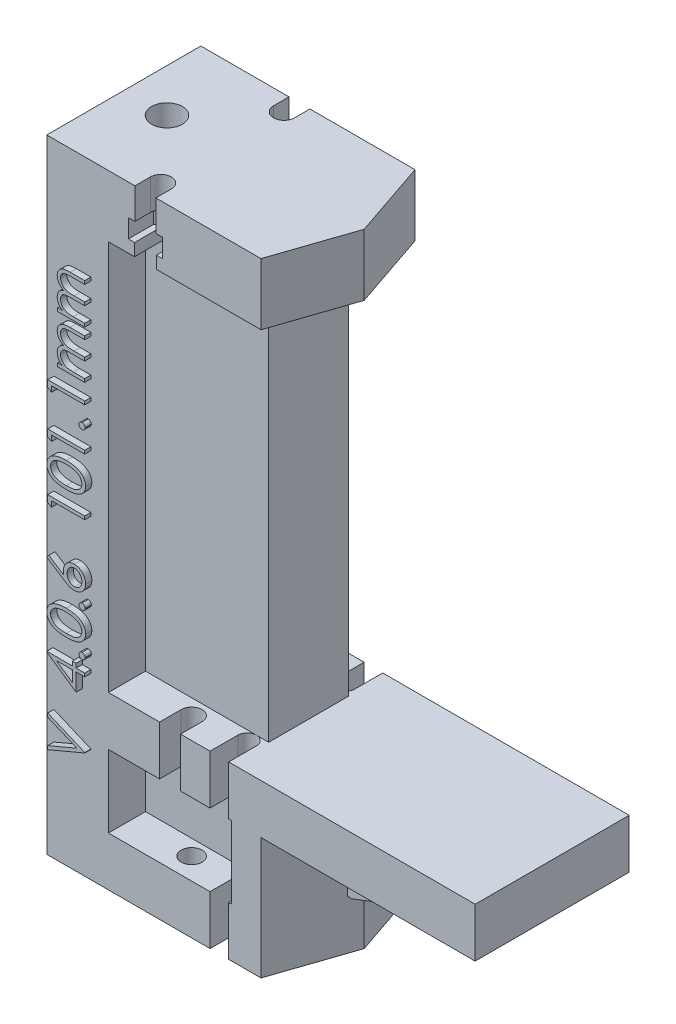
SolidWorks part; units mm, degrees
material "ABS"
ref_plane "Front" through (0, 0, 0) normal (0, 0, 1) x (1, 0, 0)
ref_plane "Top" through (0, 0, 0) normal (0, 1, 0) x (1, 0, 0)
ref_plane "Right" through (0, 0, 0) normal (1, 0, 0) x (0, 0, -1)
sketch "Sketch6" plane through (0, 0, 0) normal (0, 0, 1) x (1, 0, 0)
  line L0 (-25, 50.55) -> (15, 50.55)
  line L1 (15, 50.55) -> (15, 42.55)
  line L2 (15, 42.55) -> (-15, 42.55)
  line L3 (-15, 42.55) -> (-15, -42.55)
  line L4 (-15, -42.55) -> (25, -42.55)
  line L5 (25, -42.55) -> (25, -50.55)
  line L6 (25, -50.55) -> (-25, -50.55)
  line L7 (-25, -50.55) -> (-25, 50.55)
  line L8 (-25, 50.55) -> (25, -50.55) construction
  dimension "D1" = 101.1
  dimension "D2" = 8
  dimension "D3" = 10
  dimension "D4" = 50
  dimension "D5" = 40
extrude "Boss-Extrude2" add sketch "Sketch6" along normal mid plane 25
sketch "Sketch15" plane through (0, 0, 12.5) normal (0, 0, 1) x (1, 0, 0)
  line L0 (-15, -22.805) -> (15, -22.805)
  line L1 (-15, -42.55) -> (-15, 42.55) construction
  line L2 (-15, -30.805) -> (5, -30.805)
  line L3 (5, -50.55) -> (15, -50.55)
  line L4 (15, -50.55) -> (15, -22.805)
  line L5 (-25, -50.55) -> (25, -50.55) construction
  line L6 (-15, -30.805) -> (-15, -22.805)
  line L7 (5, -50.55) -> (5, -30.805)
  dimension "D2" = 8
extrude "Boss-Extrude3" add sketch "Sketch15" against normal up to surface (25 mm away) up to face at (0, 0, -12.5)
sketch "Sketch20" plane through (0, 50.55, 0) normal (0, 1, 0) x (1, 0, 0)
  line L0 (-10.7, 12.5) -> (-10.7, 10)
  line L1 (15, 12.5) -> (-25, 12.5) construction
  line L2 (-7.3, 10) -> (-7.3, 12.5)
  line L3 (-7.3, 12.5) -> (-10.7, 12.5)
  line L4 (0, 0) -> (15, 0) construction
  line L5 (15, -12.5) -> (15, 12.5) construction
  line L6 (-7.3, -12.5) -> (-10.7, -12.5)
  line L7 (-7.3, -10) -> (-7.3, -12.5)
  line L8 (-10.7, -12.5) -> (-10.7, -10)
  line L9 (-9, -10) -> (-9, 10) construction
  arc A0 (-10.7, 10) -> (-7.3, 10) centre (-9, 10) ccw
  arc A1 (-10.7, -10) -> (-7.3, -10) centre (-9, -10) cw
  dimension "D1" = 1.7
  dimension "D2" = 20
extrude "Cut-Extrude2" cut sketch "Sketch20" against normal up to next
sketch "Sketch21" plane through (0, -50.55, 0) normal (0, -1, 0) x (1, 0, 0)
  line L0 (-6.7, 12.5) -> (-6.7, 9)
  line L1 (-25, 12.5) -> (25, 12.5) construction
  line L2 (-3.3, 9) -> (-3.3, 12.5)
  line L3 (-3.3, 12.5) -> (-6.7, 12.5) construction
  line L4 (-5, -9) -> (-5, 9) construction
  line L5 (-6.7, 12.5) -> (-3.3, 12.5)
  line L7 (-3.3, -12.5) -> (-6.7, -12.5)
  line L8 (-3.3, -9) -> (-3.3, -12.5)
  line L9 (-6.7, -12.5) -> (-6.7, -9)
  arc A0 (-6.7, 9) -> (-3.3, 9) centre (-5, 9) ccw
  arc A1 (-6.7, -9) -> (-3.3, -9) centre (-5, -9) cw
  dimension "D1" = 1.7
  dimension "D2" = 18
extrude "Cut-Extrude3" cut sketch "Sketch21" against normal up to surface (27.745 mm away) up to face at (0, -22.805, 0)
sketch "Sketch22" plane through (0, 0, 0) normal (0, 0, 1) x (1, 0, 0)
  line L0 (-15, 21.805) -> (11, 42.55)
  line L1 (-7.3, 42.55) -> (15, 42.55) construction
  line L2 (-15, 42.55) -> (11, 42.55)
  line L5 (-15, -22.805) -> (-15, 42.55) construction
  line L7 (-15, 42.55) -> (-10.7, 42.55) construction
  line L8 (-15, 42.55) -> (-15, 21.805)
extrude "Boss-Extrude5" [suppressed] add sketch "Sketch22" along normal mid plane 4
sketch "Sketch23" plane through (0, 50.55, 0) normal (0, 1, 0) x (1, 0, 0)
  line L0 (-2.51, 12.5) -> (-2.51, 9)
  line L1 (15, 12.5) -> (-7.3, 12.5) construction
  line L2 (0.51, 9) -> (0.51, 12.5)
  line L3 (0.51, 12.5) -> (-2.51, 12.5)
  line L4 (-9, 10) -> (-1, 10) construction
  line L5 (-1, 10) -> (-1, 9) construction
  line L6 (0, 0) -> (12, 0) construction
  line L8 (0.51, -12.5) -> (-2.51, -12.5)
  line L9 (0.51, -9) -> (0.51, -12.5)
  line L10 (-2.51, -12.5) -> (-2.51, -9)
  line L11 (15, -12.5) -> (15, 12.5) construction
  arc A0 (-2.51, 9) -> (0.51, 9) centre (-1, 9) ccw
  arc A1 (-2.51, -9) -> (0.51, -9) centre (-1, -9) cw
  dimension "D1" = 1.51
  dimension "D2" = 8
  dimension "D3" = 1
  dimension "D4" = 3
extrude "Cut-Extrude4" [suppressed] cut sketch "Sketch23" against normal up to next
sketch "Sketch24" plane through (0, -50.55, 0) normal (0, -1, 0) x (1, 0, 0)
  line L0 (1.49, -12.5) -> (1.49, -8)
  line L1 (-3.3, -12.5) -> (25, -12.5) construction
  line L2 (4.51, -8) -> (4.51, -12.5)
  line L3 (4.51, -12.5) -> (1.49, -12.5)
  line L4 (3, -8) -> (3, -9) construction
  line L5 (3, -9) -> (-5, -9) construction
  line L9 (4.51, 12.5) -> (1.49, 12.5)
  line L10 (4.51, 8) -> (4.51, 12.5)
  line L11 (1.49, 12.5) -> (1.49, 8)
  arc A0 (1.49, -8) -> (4.51, -8) centre (3, -8) cw
  arc A1 (1.49, 8) -> (4.51, 8) centre (3, 8) ccw
  dimension "D2" = 8
  dimension "D3" = 1
extrude "Cut-Extrude6" cut sketch "Sketch24" against normal up to surface (27.745 mm away) up to face at (-3.3333, -22.805, 0)
sketch "Sketch28" plane through (0, 50.55, 0) normal (0, 1, 0) x (1, 0, 0)
  line L0 (-10.7, 10) -> (-7.3, 10) construction
  line L1 (-10.7, -10) -> (-7.3, -10) construction
  line L2 (-7.3, -12.5) -> (-7.3, -10) construction
  arc A0 (-10.7, 10) -> (-7.3, 10) centre (-9, 10) ccw construction
  arc A1 (-7.3, -10) -> (-10.7, -10) centre (-9, -10) ccw construction
sketch "Sketch29" plane through (-25, 0, 0) normal (-1, 0, 0) x (0, 0, 1)
  line L0 (-12.5, 50.55) -> (12.5, 50.55)
  line L1 (12.5, 50.55) -> (12.5, -50.55)
  line L2 (12.5, -50.55) -> (-12.9424, -50.55)
  line L3 (-12.9424, -50.55) -> (-12.5, 50.55)
extrude "Cut-Extrude7" [suppressed] cut sketch "Sketch29" against normal blind 6
sketch "Sketch30" plane through (0, -42.55, 0) normal (0, 1, 0) x (1, 0, 0)
  line L0 (25, 12.5) -> (25, -12.5)
  line L1 (25, -12.5) -> (15, -12.5)
  line L2 (15, -12.5) -> (15, 12.5)
  line L3 (15, 12.5) -> (25, 12.5)
extrude "Cut-Extrude8" cut sketch "Sketch30" against normal up to surface (8 mm away) up to face at (-0.8, -50.55, 0)
sketch "Sketch34" plane through (0, -22.805, 0) normal (0, 1, 0) x (1, 0, 0)
  line L1 (9.755, 12.5) -> (14, 0)
  line L2 (15, -12.5) -> (4.51, -12.5) construction
  line L3 (9.755, -12.5) -> (15, -12.5)
  line L6 (15, 12.5) -> (9.755, 12.5)
  line L7 (15, 12.5) -> (4.51, 12.5) construction
  line L9 (15, -12.5) -> (15, 12.5)
  line L10 (15, 0) -> (14, 0) construction
  line L11 (14, 0) -> (9.755, -12.5)
extrude "Cut-Extrude9" cut sketch "Sketch34" against normal through all both and the other way through all
sketch "Sketch35" plane through (0, 0, 12.5) normal (0, 0, 1) x (1, 0, 0)
  line L0 (-17.85, 50.55) -> (-17.85, -50.55) construction
  line L1 (-10.7, 50.55) -> (-25, 50.55) construction
  line L2 (-25, -50.55) -> (-6.7, -50.55) construction
  text T0 "V  4.0.6  101.1mm" font "Century Gothic" height 6
extrude "Boss-Extrude6" add sketch "Sketch35" along normal blind 1
sketch3d "3DSketch1"
  line L0 (4.51, -22.805, 12.5) -> (4.51, -30.805, 12.5)
  line L1 (4.51, -30.805, 12.5) -> (4.51, -30.805, -12.5)
  line L2 (4.51, -30.805, -12.5) -> (4.51, -22.805, -12.5)
  line L3 (4.51, -22.805, -12.5) -> (4.51, -22.805, 12.5)
extrude "Boss-Extrude7" add sketch "3DSketch1" along direction (1, 0, 0) on the side against the normal blind 40
sketch "Sketch37" plane through (0, 0, 0) normal (0, 0, 1) x (1, 0, 0)
  line L1 (14, -30.805) -> (44.51, -30.805)
  line L3 (5, -42.55) -> (14, -42.55) construction
  line L4 (14, -30.805) -> (14, -42.55)
  line L5 (14, -42.55) -> (44.51, -30.805)
extrude "Boss-Extrude17" add sketch "Sketch37" along direction (0, 0, 1) on the side of the normal mid plane 4 separate body
sketch "Sketch38" plane through (0, 42.55, 0) normal (0, -1, 0) x (1, 0, 0)
  line L0 (-11.75, 11.5877) -> (-11.75, 12.5) construction
  line L1 (-10.7, 10) -> (-7.3, 10) construction
  line L2 (-6.25, 8.4123) -> (-6.25, 11.5877) construction
  line L3 (-9, 6.8246) -> (-6.25, 8.4123)
  line L4 (-11.75, 8.4123) -> (-9, 6.8246)
  line L5 (-11.75, 11.5877) -> (-11.75, 8.4123) construction
  line L6 (-9, 13.1754) -> (-11.75, 11.5877) construction
  line L7 (-6.25, 11.5877) -> (-9, 13.1754) construction
  line L8 (-10.7, -10) -> (-7.3, -10) construction
  line L9 (-6.25, -11.5877) -> (-6.25, -8.4123) construction
  line L10 (-6.25, -8.4123) -> (-9, -6.8246)
  line L11 (-9, -6.8246) -> (-11.75, -8.4123)
  line L12 (-11.75, -8.4123) -> (-11.75, -11.5877) construction
  line L13 (-11.75, -11.5877) -> (-9, -13.1754) construction
  line L14 (-9, -13.1754) -> (-6.25, -11.5877) construction
  line L15 (-15, 12.5) -> (-10.7, 12.5) construction
  line L17 (-7.3, 12.5) -> (9.755, 12.5) construction
  line L18 (-6.25, 12.5) -> (-6.25, 11.5877) construction
  line L19 (-11.75, -11.5877) -> (-11.75, -12.5) construction
  line L20 (-15, -12.5) -> (-10.7, -12.5) construction
  line L21 (-11.77, -12.5) -> (-6.23, -12.5)
  line L22 (-7.3, -12.5) -> (9.755, -12.5) construction
  line L23 (-6.25, -12.5) -> (-6.25, -11.5877) construction
  line L24 (-11.77, 12.5) -> (-11.77, 8.4238)
  line L25 (-11.77, 8.4238) -> (-11.75, 8.4123)
  line L26 (-6.23, 12.5) -> (-6.23, 8.4238)
  line L27 (-6.23, 8.4238) -> (-6.25, 8.4123)
  line L28 (-11.77, 12.5) -> (-6.23, 12.5)
  line L29 (-6.25, -8.4123) -> (-6.23, -8.4238)
  line L30 (-6.23, -8.4238) -> (-6.23, -12.5)
  line L31 (-11.77, -12.5) -> (-11.77, -8.4238)
  line L32 (-11.77, -8.4238) -> (-11.75, -8.4123)
  circle A1 centre (-9, 10) radius 2.75 construction
  circle A2 centre (-9, 10) radius 3.1754 construction
  circle A3 centre (-9, -10) radius 3.1754 construction
  circle A4 centre (-9, -10) radius 2.75 construction
  point P18 (-6.25, -10)
  point P19 (-9, 10)
  point P24 (-7.625, -7.6184)
  point P25 (-10.375, -7.6184)
  dimension "D1" = 5.5
  dimension "D2" = 6
  dimension "D3" = 6.3509
  dimension "D4" = 5.5
  dimension "D5" = 6.3509
  dimension "D7" = 0.02
  dimension "D8" = 0.02
  dimension "D9" = 0.02
extrude "Cut-Extrude10" cut sketch "Sketch38" against normal blind 3
sketch "Sketch39" plane through (14, 0, 0) normal (-1, 0, 0) x (0, 0, 1)
  line L1 (-2, -42.55) -> (2, -42.55)
  line L2 (-2, -42.55) -> (-2, -30.805)
  line L3 (-2, -30.805) -> (2, -30.805)
  line L4 (2, -42.55) -> (2, -30.805)
extrude "Boss-Extrude18" add sketch "Sketch39" along normal blind 2.5
hole_wizard "Ø5.0mm Dowel Hole1" positions "Sketch41" profile "Sketch42" hole size "Ø5.0" standard "ANSI Metric"
sketch "Sketch41" plane through (0, 50.55, 0) normal (0, 1, 0) x (1, 0, 0)
  line L0 (-25, 0) -> (-18, 0) construction
  line L1 (-25, -12.5) -> (-25, 12.5) construction
  point P0 (-18, 0)
  dimension "D1" = 7
sketch "Sketch42" plane through (-18, 50.55, 0) normal (1, 0, 0) x (0, 0, 1)
  line L0 (0, 0) -> (0, 6.5022)
  line L1 (0, 6.5022) -> (2.5, 5)
  line L2 (2.5, 5) -> (2.5, 0)
  line L5 (2.5, 0) -> (0, 0)
  line L10 (0, 6.5022) -> (-2.5, 5) construction
  line L11 (0, -6.35) -> (0, 107.95) construction
  dimension "Hole Dia." = 5
  dimension "Hole Depth" = 5
  dimension "Drill Angle" = 118
sketch "Sketch43" plane through (0, 42.55, 0) normal (0, -1, 0) x (1, 0, 0)
  line L0 (-11.77, 12.5) -> (-10.77, 12.5)
  line L1 (-10.77, 12.5) -> (-10.77, 7.8465)
  line L2 (-6.23, 12.5) -> (-7.23, 12.5)
  line L3 (-7.23, 12.5) -> (-7.23, 7.8465)
  line L4 (-11.77, -12.5) -> (-10.77, -12.5)
  line L5 (-10.77, -12.5) -> (-10.77, -7.8465)
  line L6 (-6.23, -12.5) -> (-7.23, -12.5)
  line L7 (-7.23, -12.5) -> (-7.23, -7.8465)
  line L8 (5, 2) -> (5, -2)
  line L19 (-15, -12.5) -> (-11.77, -12.5)
  line L20 (-11.77, 8.4238) -> (-11.77, 12.5)
  line L21 (-11.77, -8.4238) -> (-9, -6.8246)
  line L22 (-9, -6.8246) -> (-6.23, -8.4238)
  line L23 (-11.77, 8.4238) -> (-11.77, 12.5)
  line L24 (-6.23, -12.5) -> (9.755, -12.5)
  line L25 (-6.23, -12.5) -> (9.755, -12.5)
  line L26 (9.755, -12.5) -> (14, 0)
  line L27 (9.755, -12.5) -> (14, 0)
  line L28 (-11.77, -12.5) -> (-11.77, -8.4238)
  line L29 (-6.23, 8.4238) -> (-9, 6.8246)
  line L30 (-9, 6.8246) -> (-11.77, 8.4238)
  line L31 (-11.77, -12.5) -> (-11.77, -8.4238)
  line L32 (-11.77, 12.5) -> (-15, 12.5)
  line L33 (-15, 12.5) -> (-15, -12.5)
  line L38 (-15, -12.5) -> (-11.77, -12.5)
  line L40 (-11.77, -8.4238) -> (-9, -6.8246)
  line L41 (-9, -6.8246) -> (-6.23, -8.4238)
  line L48 (-6.23, 8.4238) -> (-9, 6.8246)
  line L49 (-9, 6.8246) -> (-11.77, 8.4238)
  line L51 (-11.77, 12.5) -> (-15, 12.5)
  line L52 (-15, 12.5) -> (-15, -12.5)
  line L57 (-6.23, -8.4238) -> (-6.23, -12.5)
  line L58 (-6.23, -8.4238) -> (-6.23, -12.5)
  line L59 (-6.23, 12.5) -> (-6.23, 8.4238)
  line L60 (-6.23, 12.5) -> (-6.23, 8.4238)
  line L61 (14, 0) -> (9.755, 12.5)
  line L62 (14, 0) -> (9.755, 12.5)
  line L64 (9.755, 12.5) -> (-6.23, 12.5)
  line L65 (9.755, 12.5) -> (-6.23, 12.5)
  dimension "D2" = 1
  dimension "D3" = 1
  dimension "D4" = 1
  dimension "D5" = 1
  dimension "D1" = 0
extrude "Boss-Extrude19" add sketch "Sketch43" along normal blind 2
sketch "Sketch44" plane through (0, -50.55, 0) normal (0, -1, 0) x (1, 0, 0)
  line L0 (-6.7, -9) -> (-6.7, -12.5)
  line L1 (-6.7, -12.5) -> (-3.3, -12.5)
  line L2 (-3.3, -12.5) -> (-3.3, -9)
  line L3 (-6.7, 9) -> (-6.7, 12.5)
  line L4 (-6.7, 12.5) -> (-3.3, 12.5)
  line L5 (-3.3, 12.5) -> (-3.3, 9)
  circle A0 centre (-5, -9) radius 1.7
  circle A1 centre (-5, 9) radius 1.7
  line M8 (-3.3, 12.5) -> (-3.3, 9)
  line M10 (-6.7, 9) -> (-6.7, 12.5)
  line M14 (-6.7, -12.5) -> (-6.7, -9)
  line M16 (-3.3, -9) -> (-3.3, -12.5)
extrude "Boss-Extrude20" add sketch "Sketch44" against normal up to surface (8 mm away) contours A1 L4 M8 M10 | A0 L1 M14 M16
sketch "Sketch45" plane through (0, -22.805, 0) normal (0, 1, 0) x (1, 0, 0)
  line L0 (-15, 12.5) -> (-15, -12.5) construction
  line L1 (-15, -6.49) -> (5, -6.49)
  line L2 (-15, -6.49) -> (-15, 6.49)
  line L3 (-15, 6.49) -> (5, 6.49)
  line L4 (5, -6.49) -> (5, 6.49)
  line L5 (5, -6.49) -> (5, 6.49) construction
  line L7 (5, -12.5) -> (5, 12.5) construction
  arc A0 (1.49, 8) -> (4.51, 8) centre (3, 8) ccw construction
  arc A1 (4.51, -8) -> (1.49, -8) centre (3, -8) ccw construction
extrude "Boss-Extrude21" add sketch "Sketch45" along normal up to next and the other way up to surface other way up to face at (0.3333, -42.55, 0)
ref_plane "Plane1" through (-25, 50.55, 12.5) normal (0, 0, -1) x (-1, 0, 0)
sketch "Sketch47" plane through (0, 50.55, 0) normal (0, 1, 0) x (1, 0, 0)
  line L1 (-50.4654, -28.787) -> (42.0947, -28.787)
  line L2 (-50.4654, -28.787) -> (-50.4654, 26.08)
  line L3 (-50.4654, 26.08) -> (42.0947, 26.08)
  line L4 (42.0947, -28.787) -> (42.0947, 26.08)
